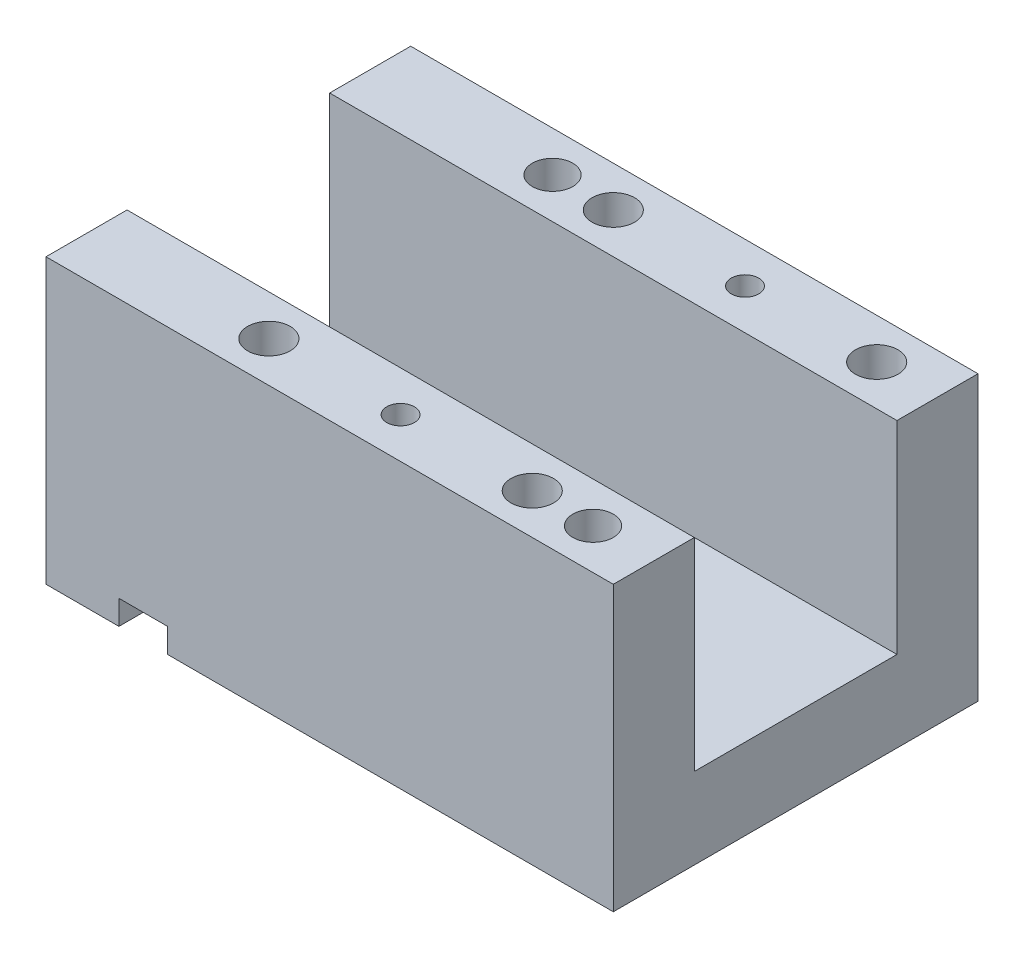
SolidWorks part; units mm, degrees
material "K110"
ref_plane "Front Plane" through (0, 0, 0) normal (0, 0, 1) x (1, 0, 0)
ref_plane "Top Plane" through (0, 0, 0) normal (0, 1, 0) x (1, 0, 0)
ref_plane "Right Plane" through (0, 0, 0) normal (1, 0, 0) x (0, 0, -1)
sketch "Sketch1" plane through (0, 0, 0) normal (0, 0, 1) x (1, 0, 0)
  line L1 (-70, -35) -> (70, -35)
  line L2 (-70, -35) -> (-70, 35)
  line L3 (-70, 35) -> (70, 35)
  line L4 (70, -35) -> (70, 35)
  line L5 (-70, -35) -> (70, 35) construction
  line L6 (-70, 35) -> (70, -35) construction
  point P0 (0, 0)
  dimension "D1" = 70
  dimension "D2" = 140
extrude "Boss-Extrude1" add sketch "Sketch1" along normal mid plane 90
sketch "Sketch2" plane through (0, 35, 0) normal (0, 1, 0) x (1, 0, 0)
  line L0 (-70, -45) -> (-70, 45) construction
  line L1 (-70, 25) -> (70, 25)
  line L2 (-70, 25) -> (-70, -25)
  line L3 (-70, -25) -> (70, -25)
  line L4 (70, 25) -> (70, -25)
  line L5 (70, -45) -> (70, 45) construction
  line L6 (-70, 0) -> (70, 0) construction
  dimension "D1" = 50
extrude "Cut-Extrude1" cut sketch "Sketch2" against normal blind 50 and the other way through all
hole_wizard "M10 Clearance Hole1" positions "Sketch10" profile "Sketch4" hole size "M10" standard "ISO" end condition through all
sketch "Sketch10" plane through (0, 35, 0) normal (0, 1, 0) x (1, 0, 0)
  line L0 (70, 35) -> (-70, 35) construction
  line L1 (70, 25) -> (70, 45) construction
  line L2 (-70, 25) -> (-70, 45) construction
  line L4 (70, -35) -> (-70, -35) construction
  line L5 (70, -45) -> (70, -25) construction
  line L6 (-70, -45) -> (-70, -25) construction
  point P0 (55, 35)
  point P2 (40, -35)
  point P4 (-25, -35)
  point P6 (-10, 35)
  point P25 (0, 0)
  point P26 (0, 0)
  point P27 (0, 0)
  point P28 (0, 0)
  dimension "D1" = 15
  dimension "D2" = 65
  dimension "D3" = 30
  dimension "D4" = 65
sketch "Sketch4" plane through (55, 35, -35) normal (1, 0, 0) x (0, 0, 1)
  line L0 (0, 0) -> (0, 70)
  line L1 (0, 70) -> (5.25, 70)
  line L2 (5.25, 70) -> (5.25, 0)
  line L5 (5.25, 0) -> (0, 0)
  line L11 (0, -6.35) -> (0, 107.95) construction
  dimension "Thru Hole Dia." = 10.5
  dimension "Thru Hole Depth" = 70
sketch "Sketch9" plane through (0, 0, 0) normal (0, 0, 1) x (1, 0, 0)
  line L0 (-70, -35) -> (70, -35) construction
  line L1 (-52, -35) -> (-40, -35)
  line L2 (-52, -35) -> (-52, -29)
  line L3 (-52, -29) -> (-40, -29)
  line L4 (-40, -35) -> (-40, -29)
  line L5 (-70, 35) -> (-70, -35) construction
  dimension "D1" = 6
  dimension "D2" = 12
  dimension "D3" = 30
extrude "Cut-Extrude2" cut sketch "Sketch9" against normal through all both and the other way through all
hole_wizard "Ø10.0mm Dowel Hole1" positions "Sketch13" profile "Sketch12" hole size "Ø10.0" standard "ISO" end condition through all
sketch "Sketch13" plane through (0, 35, 0) normal (0, 1, 0) x (1, 0, 0)
  line L0 (-70, 25) -> (-70, 45) construction
  line L1 (70, -45) -> (70, -25) construction
  line L2 (70, 25) -> (70, 45) construction
  point P0 (55, -35)
  point P2 (-25, 35)
  point P7 (-70, 35)
  point P8 (0, 0)
  point P12 (70, -35)
  dimension "D1" = 15
  dimension "D2" = 95
sketch "Sketch12" plane through (55, 35, 35) normal (1, 0, 0) x (0, 0, 1)
  line L0 (0, 0) -> (0, 70)
  line L1 (0, 70) -> (5, 70)
  line L2 (5, 70) -> (5, 0)
  line L5 (5, 0) -> (0, 0)
  line L11 (0, -6.35) -> (0, 107.95) construction
  dimension "Thru Hole Dia." = 10
  dimension "Thru Hole Depth" = 70
hole_wizard "M8 Tapped Hole1" positions "Sketch16" profile "Sketch15" tap size "M8" standard "ISO"
sketch "Sketch16" plane through (0, 35, 0) normal (0, 1, 0) x (1, 0, 0)
  line L0 (70, 25) -> (70, 45) construction
  line L1 (70, -45) -> (70, -25) construction
  point P0 (22.5, 35)
  point P2 (7.5, -35)
  point P7 (70, 35)
  point P10 (70, -35)
  dimension "D1" = 47.5
  dimension "D2" = 62.5
sketch "Sketch15" plane through (22.5, 35, -35) normal (1, 0, 0) x (0, 0, 1)
  line L0 (0, 0) -> (0, 19.75)
  line L1 (0, 19.75) -> (3.4, 17.7071)
  line L2 (3.4, 17.7071) -> (3.4, 0)
  line L5 (3.4, 0) -> (0, 0)
  line L10 (0, 19.75) -> (-3.4, 17.7071) construction
  line L11 (0, -6.35) -> (0, 107.95) construction
  dimension "Tap Drill Dia." = 6.8
  dimension "Tap Drill Depth" = 19.75
  dimension "Drill Angle" = 118
cosmetic thread "Hole Thread9"
cosmetic thread "Hole Thread10"
hole_wizard "M8 Tapped Hole2" positions "Sketch19" profile "Sketch18" tap size "M8" standard "ISO"
sketch "Sketch19" plane through (-70, 0, 0) normal (-1, 0, 0) x (0, 0, 1)
  line L0 (45, 35) -> (25, 35) construction
  line L1 (-25, 35) -> (-45, 35) construction
  line L2 (45, -35) -> (-45, -35) construction
  point P0 (-35, 23)
  point P2 (-35, -23)
  point P4 (35, 23)
  point P6 (35, -23)
  point P11 (35, 35)
  point P14 (-35, 35)
  point P17 (0, 0)
  point P18 (0, 0)
  dimension "D1" = 12
  dimension "D2" = 12
sketch "Sketch18" plane through (-70, 23, -35) normal (0, 1, 0) x (0, 0, 1)
  line L0 (0, 0) -> (0, 19.75)
  line L1 (0, 19.75) -> (3.4, 17.7071)
  line L2 (3.4, 17.7071) -> (3.4, 0)
  line L5 (3.4, 0) -> (0, 0)
  line L10 (0, 19.75) -> (-3.4, 17.7071) construction
  line L11 (0, -6.35) -> (0, 107.95) construction
  dimension "Tap Drill Dia." = 6.8
  dimension "Tap Drill Depth" = 19.75
  dimension "Drill Angle" = 118
cosmetic thread "Hole Thread11"
cosmetic thread "Hole Thread12"
cosmetic thread "Hole Thread13"
cosmetic thread "Hole Thread14"
